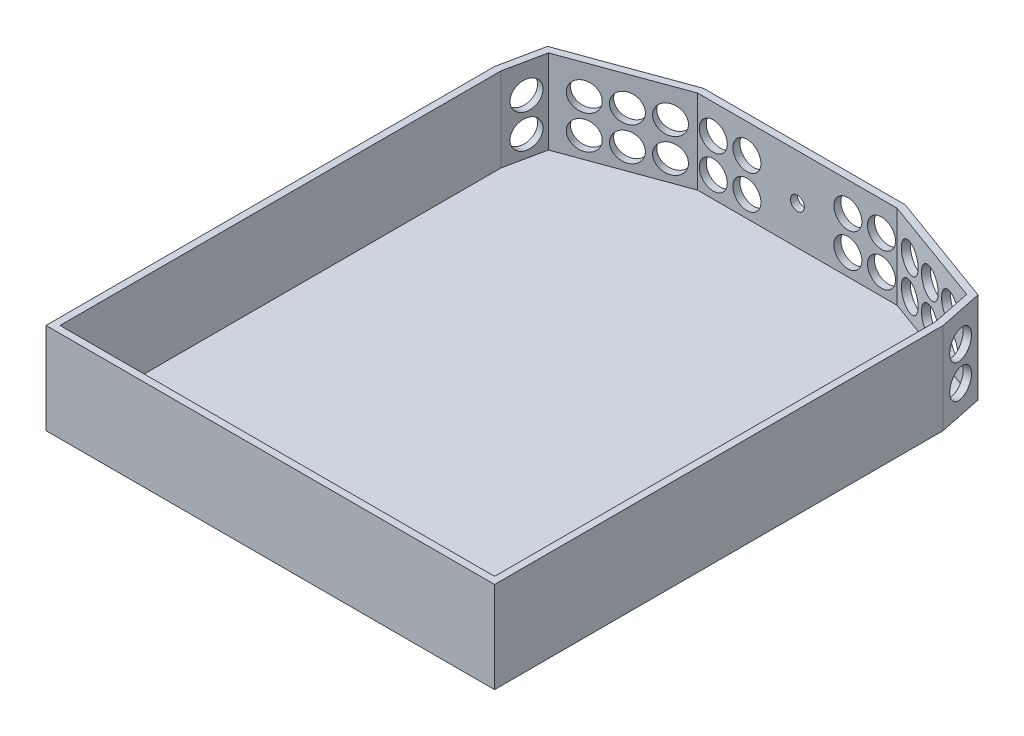
SolidWorks part; units mm, degrees
material "ABS"
ref_plane "Front Plane" through (0, 0, 0) normal (0, 0, 1) x (1, 0, 0)
ref_plane "Top Plane" through (0, 0, 0) normal (0, 1, 0) x (1, 0, 0)
ref_plane "Right Plane" through (0, 0, 0) normal (1, 0, 0) x (0, 0, -1)
sketch "Sketch1" plane through (0, 0, 0) normal (0, 1, 0) x (1, 0, 0)
  line L0 (-80, 0) -> (0, 0) construction
  line L1 (36, 110.505) -> (-36, 110.505)
  line L2 (-80, 80) -> (-80, -80)
  line L3 (-80, -80) -> (80, -80)
  line L4 (-36, 110.505) -> (-76.7619, 95.6689)
  line L5 (36, 110.505) -> (76.7619, 95.6689)
  line L6 (80, 80) -> (76.7619, 95.6689)
  line L7 (-80, 80) -> (-76.7619, 95.6689)
  line L8 (0, -80) -> (0, 110.505) construction
  line L9 (80, 80) -> (80, -80)
  point P0 (0, 0)
  dimension "D3" = 191.676
  dimension "D6" = 36
  dimension "D1" = 16
  dimension "D2" = 160
  dimension "D4" = 200
  dimension "D5" = 80
extrude "Boss-Extrude1" add sketch "Sketch1" along normal blind 2.5
sketch "Sketch3" plane through (0, 2.5, 0) normal (0, 1, 0) x (1, 0, 0)
  line L6 (-80, 80) -> (-80, -80)
  line L7 (-80, -80) -> (80, -80)
  line L8 (-76.7619, 95.6689) -> (-80, 80)
  line L9 (-80, 80) -> (-80, -80)
  line L10 (-80, -80) -> (80, -80)
  line L11 (-76.7619, 95.6689) -> (-80, 80)
  line L14 (80, -80) -> (80, 80)
  line L15 (-77.5, 79.7444) -> (-77.5, -77.5)
  line L16 (-77.5, -77.5) -> (77.5, -77.5)
  line L17 (-74.596, 93.7968) -> (-77.5, 79.7444)
  line L18 (-77.5, 79.7444) -> (-77.5, -77.5)
  line L19 (-77.5, -77.5) -> (77.5, -77.5)
  line L20 (-74.596, 93.7968) -> (-77.5, 79.7444)
  line L21 (80, -80) -> (80, 80)
  line L22 (80, 80) -> (76.7619, 95.6689)
  line L23 (80, 80) -> (76.7619, 95.6689)
  line L24 (76.7619, 95.6689) -> (36, 110.505)
  line L25 (76.7619, 95.6689) -> (36, 110.505)
  line L26 (36, 110.505) -> (-36, 110.505)
  line L27 (36, 110.505) -> (-36, 110.505)
  line L28 (-36, 110.505) -> (-76.7619, 95.6689)
  line L29 (-36, 110.505) -> (-76.7619, 95.6689)
  line L30 (77.5, -77.5) -> (77.5, 79.7444)
  line L31 (77.5, -77.5) -> (77.5, 79.7444)
  line L32 (77.5, 79.7444) -> (74.596, 93.7968)
  line L33 (77.5, 79.7444) -> (74.596, 93.7968)
  line L34 (74.596, 93.7968) -> (35.5592, 108.005)
  line L35 (74.596, 93.7968) -> (35.5592, 108.005)
  line L36 (35.5592, 108.005) -> (-35.5592, 108.005)
  line L37 (35.5592, 108.005) -> (-35.5592, 108.005)
  line L38 (-35.5592, 108.005) -> (-74.596, 93.7968)
  line L39 (-35.5592, 108.005) -> (-74.596, 93.7968)
  dimension "D1" = 0
  dimension "D2" = 2.5
extrude "Boss-Extrude2" add sketch "Sketch3" along normal blind 30
sketch "Sketch4" plane through (0, 0, -110.505) normal (0, 0, -1) x (-1, 0, 0)
  line L0 (0, 0) -> (0, 32.5) construction
  line L1 (-36, 32.5) -> (36, 32.5) construction
  line L2 (-36, 0) -> (36, 0) construction
  circle A0 centre (-30, 10) radius 5
  circle A1 centre (-18, 10) radius 5
  circle A2 centre (0, 16.25) radius 2.5
  circle A4 centre (18, 10) radius 5
  circle A5 centre (30, 10) radius 5
  circle A6 centre (-18, 22) radius 5
  circle A9 centre (18, 22) radius 5
  circle A10 centre (30, 22) radius 5
  circle A11 centre (-30, 22) radius 5
  circle A12 centre (-6, 22) radius 5 [skipped]
  circle A13 centre (-6, 10) radius 5 [skipped]
  circle A14 centre (6, 10) radius 5 [skipped]
  circle A15 centre (6, 22) radius 5 [skipped]
  dimension "D1" = 10
  dimension "D2" = 10
  dimension "D6" = 5
  dimension "D3" = 30
  dimension "D4" = 6
  dimension "D5" = 2
extrude "Cut-Extrude1" cut sketch "Sketch4" against normal up to surface (2.5 mm away) up to face at (0, 17.5, -108.005)
sketch "Sketch5" plane through (39.7268, 0, -109.1486) normal (0.342, 0, -0.9397) x (-0.9397, 0, -0.342)
  line L0 (-39.4119, 0) -> (3.966, 0) construction
  line L1 (3.966, 32.5) -> (3.966, 0) construction
  line L2 (-4.034, 10) -> (-16.034, 10) construction
  circle A0 centre (-4.034, 10) radius 5
  circle A1 centre (-16.034, 10) radius 5
  circle A2 centre (-28.034, 10) radius 5
  circle A3 centre (-16.034, 22) radius 5
  circle A4 centre (-28.034, 22) radius 5
  circle A5 centre (-4.034, 22) radius 5
  dimension "D1" = 10
  dimension "D2" = 10
  dimension "D3" = 8
  dimension "D6" = 12
  dimension "D4" = 3
  dimension "D5" = 2
extrude "Cut-Extrude2" cut sketch "Sketch5" against normal up to next
sketch "Sketch6" plane through (92.5788, 0, -19.1321) normal (0.9793, 0, -0.2024) x (-0.2024, 0, -0.9793)
  line L0 (78.154, 32.5) -> (78.154, 0) construction
  line L2 (62.154, 0) -> (78.154, 0) construction
  circle A0 centre (70.154, 10) radius 5
  circle A3 centre (70.154, 22) radius 5
  circle A4 centre (58.154, 22) radius 5 [skipped]
  circle A5 centre (58.154, 10) radius 5 [skipped]
  dimension "D2" = 10
  dimension "D1" = 10
  dimension "D4" = 8
  dimension "D3" = 2
  dimension "D5" = 2
extrude "Cut-Extrude3" cut sketch "Sketch6" against normal up to next
sketch "Sketch7" plane through (-39.7268, 0, -109.1486) normal (-0.342, 0, -0.9397) x (-0.9397, 0, 0.342)
  line L0 (-3.966, 0) -> (39.4119, 0) construction
  line L1 (-3.966, 32.5) -> (-3.966, 0) construction
  circle A0 centre (4.034, 10) radius 5
  circle A1 centre (16.034, 10) radius 5
  circle A2 centre (28.034, 10) radius 5
  circle A3 centre (16.034, 22) radius 5
  circle A4 centre (28.034, 22) radius 5
  circle A5 centre (4.034, 22) radius 5
  dimension "D1" = 10
  dimension "D2" = 10
  dimension "D3" = 8
  dimension "D4" = 3
  dimension "D5" = 2
extrude "Cut-Extrude4" cut sketch "Sketch7" against normal up to next
sketch "Sketch8" plane through (-92.5788, 0, -19.1321) normal (-0.9793, 0, -0.2024) x (-0.2024, 0, 0.9793)
  line L0 (-78.154, 32.5) -> (-78.154, 0) construction
  line L1 (-78.154, 0) -> (-62.154, 0) construction
  circle A0 centre (-70.154, 10) radius 5
  circle A1 centre (-70.154, 22) radius 5
  dimension "D1" = 10
  dimension "D2" = 8
  dimension "D3" = 10
  dimension "D4" = 2
extrude "Cut-Extrude5" cut sketch "Sketch8" against normal up to next
